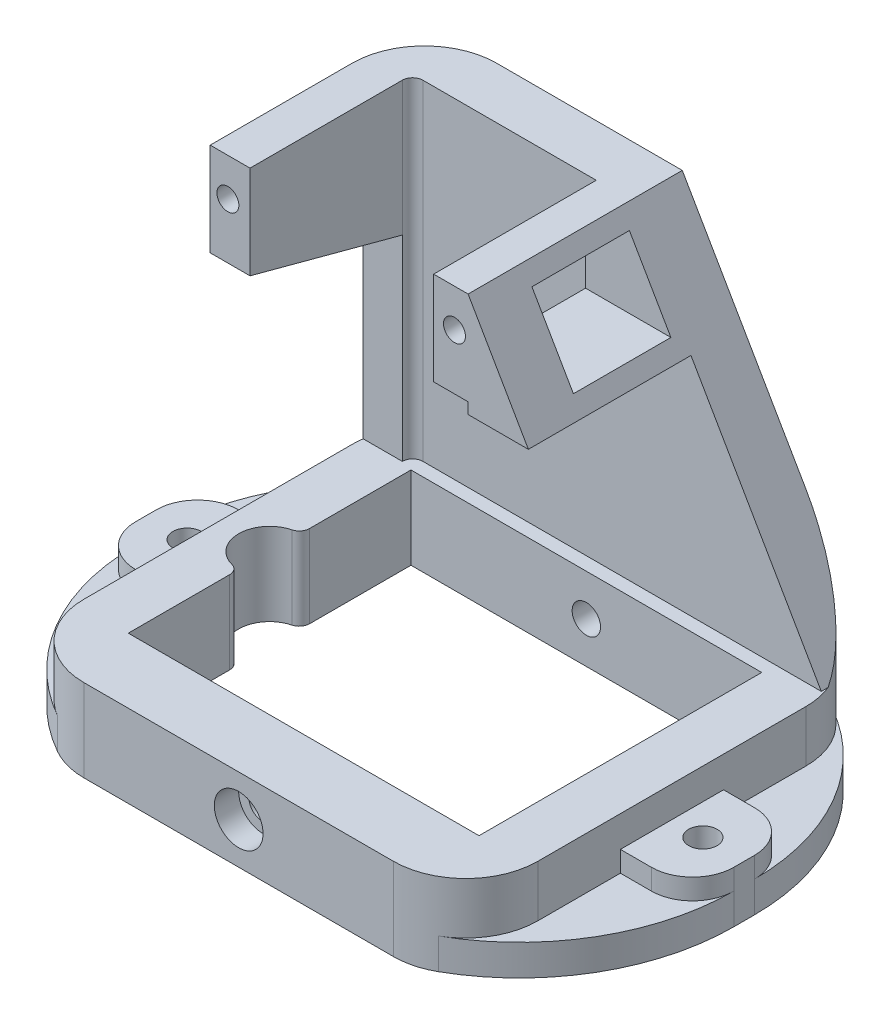
SolidWorks part; units mm, degrees
ref_plane "Front Plane" through (0, 0, 0) normal (0, 0, 1) x (1, 0, 0)
ref_plane "Top Plane" through (0, 0, 0) normal (0, 1, 0) x (1, 0, 0)
ref_plane "Right Plane" through (0, 0, 0) normal (1, 0, 0) x (0, 0, -1)
sketch "Sketch1" plane through (0, 0, 0) normal (0, 1, 0) x (1, 0, 0)
  line L1 (-21.59, 17.399) -> (21.59, 17.399)
  line L2 (-21.59, 17.399) -> (-21.59, -17.399)
  line L3 (-21.59, -17.399) -> (21.59, -17.399)
  line L4 (21.59, 17.399) -> (21.59, -17.399)
  line L5 (-21.59, 17.399) -> (21.59, -17.399) construction
  line L6 (-21.59, -17.399) -> (21.59, 17.399) construction
  line L7 (-27.94, 25.4) -> (27.94, 25.4)
  line L8 (-27.94, 25.4) -> (-27.94, -25.4)
  line L9 (-27.94, -25.4) -> (27.94, -25.4)
  line L10 (27.94, 25.4) -> (27.94, -25.4)
  line L11 (-27.94, 25.4) -> (27.94, -25.4) construction
  line L12 (-27.94, -25.4) -> (27.94, 25.4) construction
  circle A0 centre (0, 0) radius 38.1 construction
  point P0 (0, 0)
  point P5 (0, 0)
  dimension "D5" = 76.2
  dimension "D1" = 34.798
  dimension "D2" = 43.18
  dimension "D3" = 50.8
  dimension "D4" = 55.88
extrude "Boss-Extrude1" add sketch "Sketch1" along normal blind 10.16
sketch "Sketch2" plane through (0, 0, 25.4) normal (0, 0, 1) x (1, 0, 0)
  line L1 (-27.94, 10.16) -> (-27.94, 0) construction
  circle A0 centre (0, 5.08) radius 1.75
  point P2 (-27.94, 5.08)
  dimension "D1" = 3.5
extrude "Cut-Extrude1" cut sketch "Sketch2" against normal through all
sketch "Sketch3" plane through (0, 0, 25.4) normal (0, 0, 1) x (1, 0, 0)
  circle A0 centre (0, 5.08) radius 3
  dimension "D1" = 6
extrude "Cut-Extrude2" cut sketch "Sketch3" against normal blind 3
chamfer "Chamfer1" [suppressed] distance 0.635 angle 85 tangent propagation no
sketch "Sketch4" plane through (0, 10.16, 0) normal (0, 1, 0) x (1, 0, 0)
  line L1 (-27.94, 25.4) -> (3.81, 25.4)
  line L2 (-27.94, 25.4) -> (-27.94, 19.05)
  line L3 (-27.94, 19.05) -> (3.81, 19.05)
  line L4 (3.81, 25.4) -> (3.81, 19.05)
  line L5 (-27.94, 19.05) -> (-23.0378, 19.05)
  line L6 (-27.94, 19.05) -> (-27.94, -0.9652)
  line L7 (-27.94, -0.9652) -> (-23.0378, -0.9652)
  line L8 (-23.0378, 19.05) -> (-23.0378, -0.9652)
  line M2 (27.94, 25.4) -> (-27.94, 25.4)
  line M3 (-27.94, 25.4) -> (-27.94, -25.4)
  dimension "D1" = 6.35
  dimension "D2" = 31.75
  dimension "D3" = 26.3652
  dimension "D4" = 4.9022
extrude "Boss-Extrude2" add sketch "Sketch4" along normal blind 40.64 contours L8 L3 L7 M3 | L4 L3 M2 M3 region at (-12.065, 10.16, -22.225) region at (-25.4889, 10.16, -9.0424)
sketch "Sketch5" plane through (-23.0378, 0, 0) normal (1, 0, 0) x (0, 0, -1)
  line L1 (-0.9652, 50.8) -> (-0.9652, 10.16) construction
  line L2 (-0.9652, 39.3128) -> (-0.9652, 10.16)
  line L3 (-0.9652, 10.16) -> (19.05, 10.16)
  line L4 (17.78, 10.16) -> (17.78, 34.29)
  line L5 (17.78, 34.29) -> (-0.9652, 39.3128)
  line L6 (19.05, 50.8) -> (19.05, 10.16) construction
  line M4 (-0.9652, 10.16) -> (19.05, 10.16)
  line M7 (-0.9652, 50.8) -> (-0.9652, 10.16)
  dimension "D1" = 1.27
  dimension "D2" = 24.13
  dimension "D3" = 75
extrude "Cut-Extrude3" cut sketch "Sketch5" against normal through all contours L4 L5 M7 M4 region at (-23.0378, 23.5201, -8.1129)
fillet "Fillet1" radius 8.89 4 edges at (-27.94, 5.08, 25.4) (-27.94, 25.4, -25.4) (27.94, 5.08, -25.4) (27.94, 5.08, 25.4)
chamfer "Chamfer2" distance 40.64 angle 30 1 edges at (3.81, 10.16, -22.225) first distance on face at (3.81, 30.48, -22.225)
sketch "Sketch6" plane through (0, 0, -19.05) normal (0, 0, 1) x (1, 0, 0)
  line L0 (-23.0378, 50.8) -> (-23.0378, 39.3128) construction
  line L1 (3.81, 50.8) -> (-0.4318, 50.8)
  line L2 (3.81, 50.8) -> (3.81, 39.3128)
  line L3 (3.81, 39.3128) -> (-0.4318, 39.3128)
  line L4 (-0.4318, 50.8) -> (-0.4318, 39.3128)
  line L5 (-27.94, 39.3128) -> (-23.0378, 39.3128) construction
  dimension "D1" = 22.606
extrude "Boss-Extrude3" add sketch "Sketch6" along normal up to surface (20.0152 mm away) up to face at (-25.4889, 45.0564, 0.9652)
sketch "Sketch8" plane through (0, 0, -19.05) normal (0, 0, 1) x (1, 0, 0)
  line L0 (3.81, 50.8) -> (3.81, 37.9516)
  line L1 (3.81, 39.3128) -> (3.81, 50.8) construction
  line L2 (3.81, 37.9516) -> (11.228, 37.9516)
  line L3 (27.2735, 10.16) -> (3.81, 50.8) construction
  line L4 (11.228, 37.9516) -> (3.81, 50.8)
extrude "Boss-Extrude5" add sketch "Sketch8" along normal up to surface (20.0152 mm away) up to face at (1.6891, 45.0564, 0.9652)
sketch "Sketch9" plane through (0, 0, 0.9652) normal (0, 0, 1) x (1, 0, 0)
  circle A0 centre (2.1319, 46.132) radius 1.35
  circle A1 centre (-25.762, 46.132) radius 1.35
  dimension "D1" = 2.7
  dimension "D2" = 2.7
extrude "Cut-Extrude4" cut sketch "Sketch9" against normal blind 8
fillet "Fillet2" radius 1.27 1 edges at (-23.0378, 30.48, -19.05)
mirror "Mirror1" about plane through (0, 0, 0) normal (0, 0, 1) of "Cut-Extrude2"
sketch "Sketch10" plane through (0, 0, 0) normal (0, -1, 0) x (1, 0, 0)
  line L7 (-27.94, 0) -> (-27.94, 6.35)
  line L8 (-27.94, -16.51) -> (-27.94, 16.51) construction
  line L14 (-27.94, 6.35) -> (-31.75, 6.35)
  line L15 (-36.83, 1.27) -> (-36.83, -1.27)
  line L16 (-31.75, -6.35) -> (-27.94, -6.35)
  line L17 (-27.94, -6.35) -> (-27.94, 0)
  arc A4 (-36.83, -1.27) -> (-31.75, -6.35) centre (-31.75, -1.27) ccw
  arc A5 (-31.75, 6.35) -> (-36.83, 1.27) centre (-31.75, 1.27) ccw
  point P12 (-36.83, 6.35)
  dimension "D1" = 6.35
  dimension "D2" = 8.89
  dimension "D3" = 5.08
extrude "Boss-Extrude6" add sketch "Sketch10" against normal blind 6.35
mirror "Mirror2" about plane through (0, 0, 0) normal (1, 0, 0) of "Boss-Extrude6"
sketch "Sketch11" plane through (0, 0, 0) normal (0, -1, 0) x (1, 0, 0)
  line L0 (-36.83, 0) -> (-31.75, 0) construction
  line L1 (-36.83, 1.27) -> (-36.83, -1.27) construction
  line L2 (31.75, 0) -> (36.83, 0) construction
  line L3 (36.83, 1.27) -> (36.83, -1.27) construction
  circle A0 centre (-31.75, 0) radius 1.75
  circle A1 centre (31.75, 0) radius 1.75
  dimension "D1" = 3.5
  dimension "D2" = 3.5
  dimension "D3" = 31.75
  dimension "D4" = 31.75
extrude "Cut-Extrude5" cut sketch "Sketch11" against normal blind 25.4
sketch "Sketch12" plane through (0, 0, 0) normal (0, -1, 0) x (1, 0, 0)
  line L0 (36.83, 1.27) -> (36.83, -1.27) construction
  line L1 (0, 0) -> (0, 17.399) construction
  line L2 (-21.59, 17.399) -> (21.59, 17.399) construction
  line L3 (0, 0) -> (-21.59, 0) construction
  line L4 (-21.59, -17.399) -> (-21.59, 17.399) construction
  line L13 (19.05, 25.4) -> (-19.05, 25.4)
  line L14 (-27.94, 16.51) -> (-27.94, 6.35)
  line L15 (-27.94, 6.35) -> (-31.75, 6.35)
  line L16 (-36.83, 1.27) -> (-36.83, -1.27)
  line L17 (-31.75, -6.35) -> (-27.94, -6.35)
  line L18 (-27.94, -6.35) -> (-27.94, -16.51)
  line L19 (-19.05, -25.4) -> (19.05, -25.4)
  line L20 (27.94, -16.51) -> (27.94, -6.35)
  line L21 (27.94, -6.35) -> (31.75, -6.35)
  line L22 (36.83, -1.27) -> (36.83, 1.27)
  line L23 (31.75, 6.35) -> (27.94, 6.35)
  line L24 (27.94, 6.35) -> (27.94, 16.51)
  line L25 (19.05, 25.4) -> (-19.05, 25.4)
  line L26 (-27.94, 16.51) -> (-27.94, 6.35)
  line L27 (-27.94, 6.35) -> (-31.75, 6.35)
  line L28 (-36.83, 1.27) -> (-36.83, -1.27)
  line L29 (-31.75, -6.35) -> (-27.94, -6.35)
  line L30 (-27.94, -6.35) -> (-27.94, -16.51)
  line L31 (-19.05, -25.4) -> (19.05, -25.4)
  line L32 (27.94, -16.51) -> (27.94, -6.35)
  line L33 (27.94, -6.35) -> (31.75, -6.35)
  line L34 (36.83, -1.27) -> (36.83, 1.27)
  line L35 (31.75, 6.35) -> (27.94, 6.35)
  line L36 (27.94, 6.35) -> (27.94, 16.51)
  arc A0 (23.4259, 24.2484) -> (36.83, 1.27) centre (10.4321, 1.27) cw
  arc A1 (27.94, 16.51) -> (19.05, 25.4) centre (19.05, 16.51) ccw construction
  arc A2 (-23.4259, 24.2484) -> (-36.83, 1.27) centre (-10.4321, 1.27) ccw
  arc A3 (23.4259, -24.2484) -> (36.83, -1.27) centre (10.4321, -1.27) ccw
  arc A4 (-23.4259, -24.2484) -> (-36.83, -1.27) centre (-10.4321, -1.27) cw
  arc A10 (-19.05, 25.4) -> (-27.94, 16.51) centre (-19.05, 16.51) ccw
  arc A11 (-31.75, 6.35) -> (-36.83, 1.27) centre (-31.75, 1.27) ccw
  arc A12 (-36.83, -1.27) -> (-31.75, -6.35) centre (-31.75, -1.27) ccw
  arc A13 (-27.94, -16.51) -> (-19.05, -25.4) centre (-19.05, -16.51) ccw
  arc A14 (19.05, -25.4) -> (27.94, -16.51) centre (19.05, -16.51) ccw
  arc A15 (31.75, -6.35) -> (36.83, -1.27) centre (31.75, -1.27) ccw
  arc A16 (36.83, 1.27) -> (31.75, 6.35) centre (31.75, 1.27) ccw
  arc A17 (27.94, 16.51) -> (19.05, 25.4) centre (19.05, 16.51) ccw
  arc A18 (-19.05, 25.4) -> (-27.94, 16.51) centre (-19.05, 16.51) ccw
  arc A19 (-31.75, 6.35) -> (-36.83, 1.27) centre (-31.75, 1.27) ccw
  arc A20 (-36.83, -1.27) -> (-31.75, -6.35) centre (-31.75, -1.27) ccw
  arc A21 (-27.94, -16.51) -> (-19.05, -25.4) centre (-19.05, -16.51) ccw
  arc A22 (19.05, -25.4) -> (27.94, -16.51) centre (19.05, -16.51) ccw
  arc A23 (31.75, -6.35) -> (36.83, -1.27) centre (31.75, -1.27) ccw
  arc A24 (36.83, 1.27) -> (31.75, 6.35) centre (31.75, 1.27) ccw
  arc A25 (27.94, 16.51) -> (19.05, 25.4) centre (19.05, 16.51) ccw
  arc M26 (-19.05, 25.4) -> (-27.94, 16.51) centre (-19.05, 16.51) ccw
  line M27 (-27.94, 16.51) -> (-27.94, 6.35)
  line M28 (-27.94, 6.35) -> (-31.75, 6.35)
  arc M29 (-31.75, 6.35) -> (-36.83, 1.27) centre (-31.75, 1.27) ccw
  arc M31 (-36.83, -1.27) -> (-31.75, -6.35) centre (-31.75, -1.27) ccw
  line M32 (-31.75, -6.35) -> (-27.94, -6.35)
  line M33 (-27.94, -6.35) -> (-27.94, -16.51)
  arc M34 (-27.94, -16.51) -> (-19.05, -25.4) centre (-19.05, -16.51) ccw
  arc M36 (19.05, -25.4) -> (27.94, -16.51) centre (19.05, -16.51) ccw
  line M37 (27.94, -16.51) -> (27.94, -6.35)
  line M38 (27.94, -6.35) -> (31.75, -6.35)
  arc M39 (31.75, -6.35) -> (36.83, -1.27) centre (31.75, -1.27) ccw
  arc M41 (36.83, 1.27) -> (31.75, 6.35) centre (31.75, 1.27) ccw
  line M42 (31.75, 6.35) -> (27.94, 6.35)
  line M43 (27.94, 6.35) -> (27.94, 16.51)
  arc M44 (27.94, 16.51) -> (19.05, 25.4) centre (19.05, 16.51) ccw
  dimension "D1" = 0
extrude "Boss-Extrude7" add sketch "Sketch12" against normal blind 3.81 contours A2 M26 M29 M28 M27 | A4 M34 M33 M32 M31 | A3 M36 M39 M38 M37 | A0 M44 M43 M42 M41 region at (31.2022, 0, 11.796) region at (-31.2022, 0, 11.796) region at (31.2022, 0, -11.796) region at (-31.2022, 0, -11.796)
ref_plane "Plane1" through (11.5682, 0, 0) normal (-1, 0, 0) x (0, 0, 1)
sketch "Sketch13" plane through (11.5682, 0, 0) normal (-1, 0, 0) x (0, 0, 1)
  line L0 (-25.4, 50.8) -> (0.9652, 50.8) construction
  line L1 (-17.7348, 48.8) -> (-5.7348, 48.8)
  line L2 (-17.7348, 48.8) -> (-17.7348, 39.9516)
  line L3 (-17.7348, 39.9516) -> (-5.7348, 39.9516)
  line L4 (-5.7348, 48.8) -> (-5.7348, 39.9516)
  line L5 (0.9652, 37.9516) -> (-19.05, 37.9516) construction
  dimension "D1" = 6.7
  dimension "D2" = 12
  dimension "D3" = 2
  dimension "D4" = 2
extrude "Cut-Extrude6" cut sketch "Sketch13" along normal up to next
sketch "Sketch14" [suppressed] plane through (0, 10.16, 0) normal (0, 1, 0) x (1, 0, 0)
  line L0 (-22.225, -17.399) -> (-22.225, 17.399) construction
  line L1 (-22.225, 3.81) -> (-22.225, -3.81)
  arc A0 (-22.225, 3.81) -> (-22.225, -3.81) centre (-22.225, 0) ccw
  point P7 (-22.225, 0)
  dimension "D1" = 3.81
sketch "Sketch15" plane through (0, 10.16, 0) normal (0, 1, 0) x (1, 0, 0)
  line L0 (-21.59, 17.399) -> (-21.59, -17.399) construction
  line L1 (-21.59, 3.81) -> (-21.59, -3.81)
  arc A0 (-21.59, 3.81) -> (-21.59, -3.81) centre (-21.59, 0) ccw
  point P8 (-21.59, 0)
  dimension "D1" = 3.81
extrude "Cut-Extrude9" cut sketch "Sketch15" against normal up to next
fillet "Fillet3" radius 1.27 2 edges at (-21.59, 5.08, 3.81) (-21.59, 5.08, -3.81)
